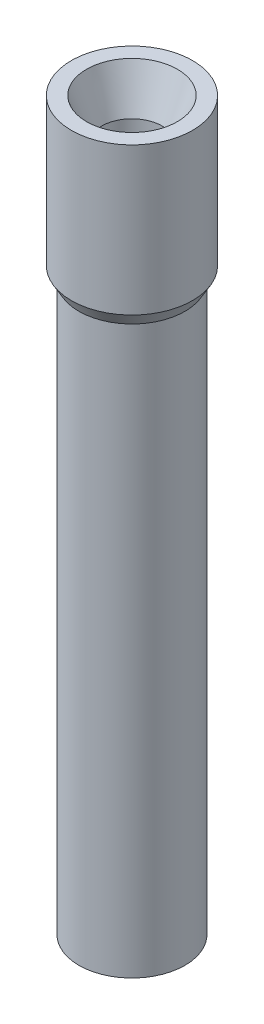
SolidWorks part; units mm, degrees
ref_plane "前视基准面" through (0, 0, 0) normal (0, 0, 1) x (1, 0, 0)
ref_plane "上视基准面" through (0, 0, 0) normal (0, 1, 0) x (1, 0, 0)
ref_plane "右视基准面" through (0, 0, 0) normal (1, 0, 0) x (0, 0, -1)
other "Configuration Table"
sketch "草图1" plane through (0, 0, 0) normal (0, 1, 0) x (1, 0, 0)
  circle A0 centre (0, 0) radius 4
  circle A1 centre (0, 0) radius 3.5
extrude "凸台-拉伸1" add sketch "草图1" along normal blind 8 contours A0
sketch "草图2" plane through (0, 0, 0) normal (0, -1, 0) x (1, 0, 0)
  circle A0 centre (0, 0) radius 3.5
extrude "凸台-拉伸2" add sketch "草图2" along normal blind 40
chamfer "倒角1" distance 1.5 angle 60 1 edges at (0, 0, -3.5) first distance on face at (0, 0, -3.5)
sketch "草图3" plane through (0, -40, 0) normal (0, -1, 0) x (1, 0, 0)
  circle A0 centre (0, 0) radius 2
extrude "切除-拉伸1" cut sketch "草图3" against normal blind 101
chamfer "倒角2" distance 1 angle 70 1 edges at (0, 8, 2) first distance on face at (0, 8, 2)
